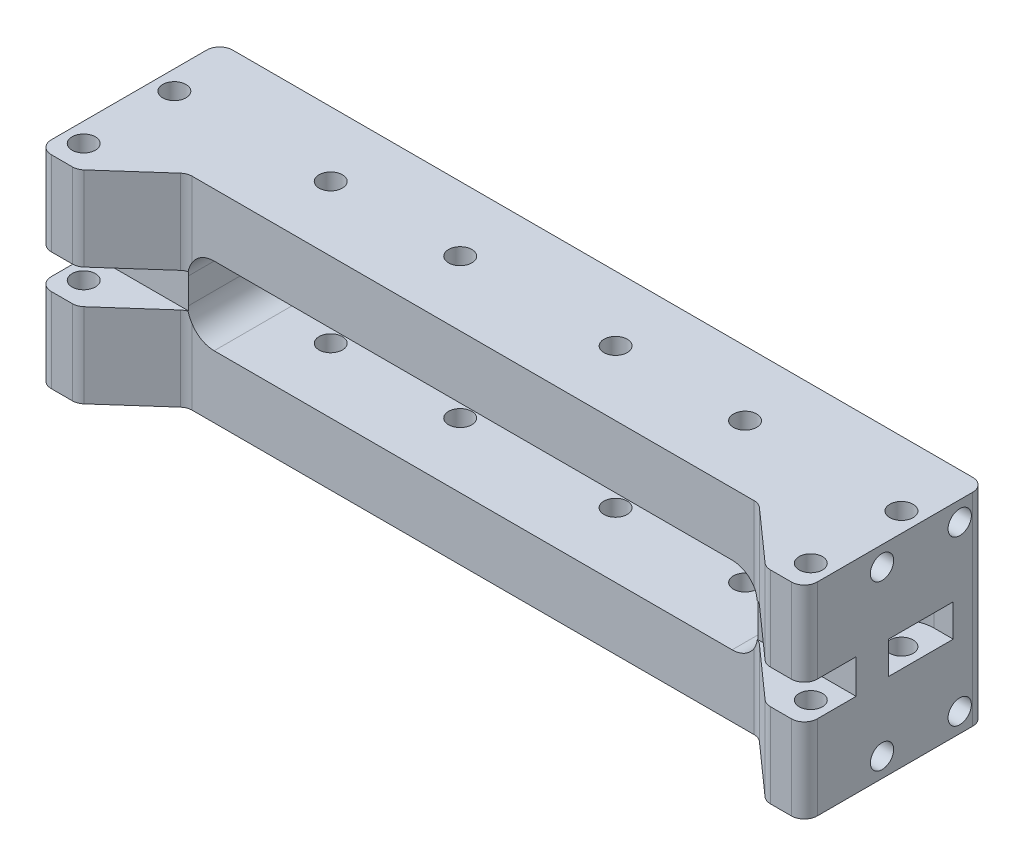
SolidWorks part; units mm, degrees
ref_plane "Front Plane" through (0, 0, 0) normal (0, 0, 1) x (1, 0, 0)
ref_plane "Top Plane" through (0, 0, 0) normal (0, 1, 0) x (1, 0, 0)
ref_plane "Right Plane" through (0, 0, 0) normal (1, 0, 0) x (0, 0, -1)
sketch "Sketch2" plane through (0, 0, 0) normal (0, 1, 0) x (1, 0, 0)
  line L7 (-75.1205, -12.7) -> (75.1205, -12.7)
  line L8 (-75.1205, -12.7) -> (-75.1205, 12.7)
  line L9 (-75.1205, 12.7) -> (75.1205, 12.7)
  line L10 (75.1205, -12.7) -> (75.1205, 12.7)
  line L11 (-75.1205, -12.7) -> (75.1205, 12.7) construction
  line L12 (-75.1205, 12.7) -> (75.1205, -12.7) construction
  point P0 (0, 0)
  point P6 (0, 0)
  dimension "D2" = 150.241
  dimension "D4" = 25.4
extrude "Boss-Extrude1" add sketch "Sketch2" along normal mid plane 39.751
sketch "Sketch3" plane through (75.1205, 0, 0) normal (1, 0, 0) x (0, 0, -1)
  line L0 (0, 0) -> (0, 19.8755) construction
  line L1 (-12.7, 19.8755) -> (12.7, 19.8755) construction
  line L2 (-12.7, 19.8755) -> (-12.7, -19.8755) construction
  line L3 (-12.7, -19.8755) -> (12.7, -19.8755) construction
  circle A0 centre (-7.62, 16.0655) radius 2.286
  circle A1 centre (-7.62, -16.0655) radius 2.286
  circle A2 centre (7.62, 16.0655) radius 2.286
  circle A3 centre (7.62, -16.0655) radius 2.286
  dimension "D4" = 4.572
  dimension "D1" = 5.08
  dimension "D2" = 3.81
  dimension "D3" = 3.81
extrude "Cut-Extrude1" cut sketch "Sketch3" against normal blind 50.8
sketch "Sketch4" plane through (0, 19.8755, 0) normal (0, 1, 0) x (1, 0, 0)
  line L0 (-75.1205, -12.7) -> (75.1205, -12.7) construction
  line L1 (75.1205, -12.7) -> (56.0705, -12.7)
  line L2 (75.1205, -12.7) -> (75.1205, -22.86)
  line L3 (75.1205, -22.86) -> (67.5005, -22.86)
  line L5 (56.0705, -12.7) -> (67.5005, -22.86)
  circle A0 centre (71.3105, -17.78) radius 2.286
  point P7 (71.3105, -22.86)
  dimension "D5" = 4.572
  dimension "D1" = 7.62
  dimension "D2" = 19.05
  dimension "D3" = 5.08
  dimension "D4" = 10.16
extrude "Boss-Extrude2" add sketch "Sketch4" against normal blind 16.51
sketch "Sketch5" plane through (0, 19.8755, 0) normal (0, 1, 0) x (1, 0, 0)
  circle A0 centre (71.3105, 0) radius 2.286
  point P2 (71.3105, -17.78)
  dimension "D1" = 4.572
extrude "Cut-Extrude2" cut sketch "Sketch5" against normal through all
sketch "Sketch6" plane through (0, 0, 0) normal (0, 1, 0) x (1, 0, 0)
  line L1 (71.3105, 6.35) -> (77.6605, 6.35)
  line L3 (71.3105, -6.35) -> (77.6605, -6.35)
  line L4 (77.6605, 6.35) -> (77.6605, -6.35)
  arc A0 (71.3105, 6.35) -> (71.3105, -6.35) centre (71.3105, 0) ccw
  dimension "D1" = 12.7
extrude "Cut-Extrude3" cut sketch "Sketch6" against normal mid plane 6.35
sketch "Sketch9" plane through (0, 19.8755, 0) normal (0, 1, 0) x (1, 0, 0)
  circle A0 centre (15.24, 0) radius 2.286
  circle A1 centre (40.64, 0) radius 2.286
  point P6 (0, 0)
  dimension "D1" = 4.572
  dimension "D2" = 15.24
  dimension "D3" = 25.4
extrude "Cut-Extrude5" cut sketch "Sketch9" against normal through all
sketch "Sketch7" plane through (0, 0, 12.7) normal (0, 0, 1) x (1, 0, 0)
  line L1 (55.88, -7.62) -> (-55.88, -7.62)
  line L2 (55.88, -7.62) -> (55.88, 7.62)
  line L3 (55.88, 7.62) -> (-55.88, 7.62)
  line L4 (-55.88, -7.62) -> (-55.88, 7.62)
  line L5 (55.88, -7.62) -> (-55.88, 7.62) construction
  line L6 (55.88, 7.62) -> (-55.88, -7.62) construction
  point P0 (0, 0)
  dimension "D1" = 15.24
  dimension "D2" = 111.76
extrude "Cut-Extrude4" cut sketch "Sketch7" against normal through all
mirror "Mirror2" about plane through (0, 0, 0) normal (0, 1, 0) of "Boss-Extrude2"
mirror "Mirror1" about plane through (0, 0, 0) normal (1, 0, 0) of "Cut-Extrude5", "Cut-Extrude1", "Boss-Extrude2", "Cut-Extrude2", "Cut-Extrude3", "Mirror2"
fillet "Fillet1" radius 2.54 17 edges at (-75.1205, 0, -12.7) (75.1205, 0, -12.7) (-67.5005, 11.6205, 22.86) (-75.1205, 11.6205, 22.86) (-75.1205, -11.6205, 22.86) (-67.5005, -11.6205, 22.86) (67.5005, -11.6205, 22.86) (75.1205, -11.6205, 22.86) (75.1205, 11.6205, 22.86) (67.5005, 11.6205, 22.86) (56.0705, 11.6205, 12.7) (56.0705, -11.6205, 12.7) (-56.0705, -11.6205, 12.7) (-56.0705, 11.6205, 12.7) (-75.1205, 0, 12.7) (-75.1205, 0, 6.35) (-75.1205, 0, -6.35)
fillet "Fillet2" radius 5.08 4 edges at (55.88, 7.62, 0.0606) (55.88, -7.62, 0.0606) (-55.88, 7.62, 0.0606) (-55.88, -7.62, 0.0606)
